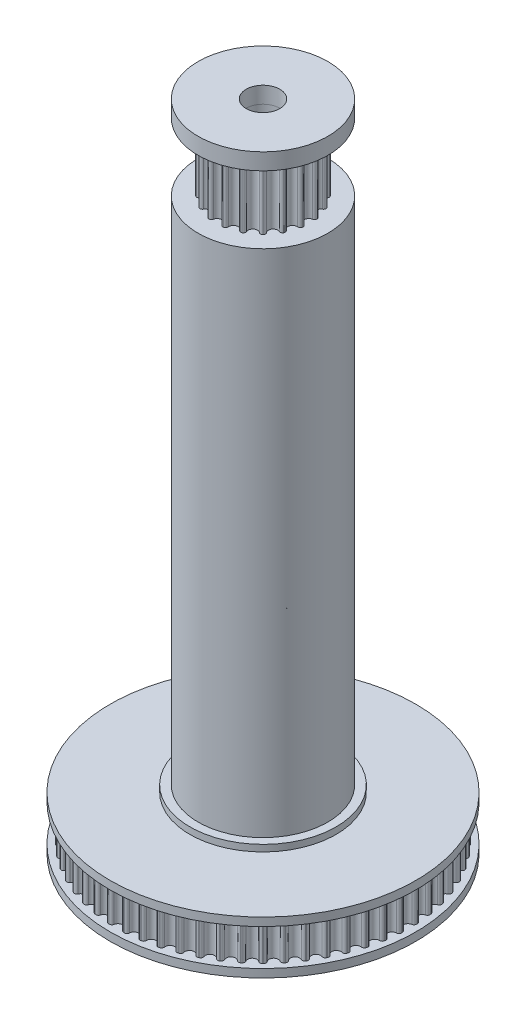
SolidWorks part; units mm, degrees
ref_plane "Front Plane" through (0, 0, 0) normal (0, 0, 1) x (1, 0, 0)
ref_plane "Top Plane" through (0, 0, 0) normal (0, 1, 0) x (1, 0, 0)
ref_plane "Right Plane" through (0, 0, 0) normal (1, 0, 0) x (0, 0, -1)
sketch "PulleyOffsets" plane through (0, 0, 0) normal (1, 0, 0) x (0, 0, -1)
  line L0 (55.5625, 0) -> (-55.5625, 0) construction
  line L1 (55.5625, 111.125) -> (-55.5625, 111.125) construction
  line L2 (0, 0) -> (0, 111.125) construction
  point P7 (0, 0)
  dimension "D1" = 111.125
ref_axis "Axis1" through (0, 34.9332, 0) along (0, -1, 0)
ref_plane "Big Pulley Plane" through (0, 0, 0) normal (0, 1, 0) x (1, 0, 0)
ref_plane "Small Pulley Plane" through (0, 111.125, 0) normal (0, 1, 0) x (1, 0, 0)
sketch "Sketch1" plane through (0, 0, 0) normal (0, 1, 0) x (1, 0, 0)
  line L0 (0, 0) -> (0, 28.2667) construction
  line L1 (0, 0) -> (2.9202, 27.7837) construction
  circle A0 centre (0, 0) radius 28.2667 construction
  circle A1 centre (0, 0) radius 27.0467 construction
  circle A2 centre (0, 27.9367) radius 0.89 construction
  circle A5 centre (2.9202, 27.7837) radius 0.89 construction
  arc A6 (0, 27.0467) -> (0.8804, 27.8061) centre (0, 27.9367) ccw
  arc A7 (0.8804, 27.8061) -> (1.3997, 28.2321) centre (1.3749, 27.7327) cw
  arc A8 (1.559, 28.2237) -> (2.031, 27.7458) centre (1.5314, 27.7245) cw
  arc A9 (2.8272, 26.8986) -> (2.031, 27.7458) centre (2.9202, 27.7837) cw
  arc A10 (1.3997, 28.2321) -> (1.559, 28.2237) centre (0, 0) cw
  arc A11 (0, 27.0467) -> (2.8272, 26.8986) centre (0, 0) ccw
  dimension "D1" = 56.5335
  dimension "D3" = 1.78
  dimension "D4" = 0.5
  dimension "D2" = 1.22
  dimension "D5" = 6
extrude "Boss-Extrude1" add sketch "Sketch1" along normal mid plane 7.112 contours A6 A11 A9 A8 A7 region at (0.001, 0, -0.0192)
pattern_circular "CirPattern1" count 60 over 360 about axis through (0, 34.9332, 0) along (0, -1, 0) of "Boss-Extrude1"
sketch "Sketch2" plane through (0, 0, 0) normal (1, 0, 0) x (0, 0, -1)
  line L10 (0, 3.5) -> (29.4415, 3.5) construction
  line L11 (0, 3.5) -> (0, 5.0875) construction
  line L12 (0, 5.0875) -> (29.4415, 5.0875) construction
  line L15 (29.4415, 3.5) -> (29.4415, 5.0875) construction
  line L20 (0, 34.9332) -> (0, -6.9932) construction
  line L22 (29.4415, 5.0875) -> (0, 5.0875)
  line L23 (29.4415, 5.0875) -> (29.4415, 3.5)
  line L24 (29.4415, 3.5) -> (0, 3.5)
  line L25 (0, 5.0875) -> (0, 3.5)
  dimension "D1" = 1.5875
  dimension "D2" = 29.4415
  dimension "D3" = 3.5
revolve "Revolve3" add sketch "Sketch2" angle 360 about axis through (0, 34.9332, 0) along (0, -1, 0) region at (0, 4.2937, -14.7207)
mirror "Mirror1" about plane through (0, 0, 0) normal (0, 1, 0) of "Revolve3"
sketch "Sketch3" plane through (0, 0, 0) normal (0, 1, 0) x (1, 0, 0)
  circle A0 centre (0, 0) radius 22.225
  dimension "D1" = 44.45
extrude "Cut-Extrude1" [suppressed] cut sketch "Sketch3" against normal through all both and the other way through all
sketch "Sketch6" plane through (0, 0, 0) normal (0, 1, 0) x (1, 0, 0)
  line L0 (0, 0) -> (0, 9.1676) construction
  line L1 (0, 0) -> (2.731, 8.405) construction
  circle A0 centre (0, 0) radius 9.1676 construction
  circle A1 centre (0, 0) radius 7.9476 construction
  circle A2 centre (0, 8.8376) radius 0.89 construction
  circle A5 centre (2.731, 8.405) radius 0.89 construction
  arc A6 (0, 7.9476) -> (0.8721, 8.6598) centre (0, 8.8376) ccw
  arc A7 (0.8721, 8.6598) -> (1.4405, 9.0537) centre (1.362, 8.5599) cw
  arc A8 (1.4277, 9.0557) -> (1.8466, 8.5054) centre (1.3498, 8.5618) cw
  arc A9 (2.4559, 7.5586) -> (1.8466, 8.5054) centre (2.731, 8.405) cw
  arc A10 (1.4405, 9.0537) -> (1.4277, 9.0557) centre (0, 0) cw construction
  arc A11 (0, 7.9476) -> (2.4559, 7.5586) centre (0, 0) ccw
  arc A12 (1.4405, 9.0537) -> (1.4277, 9.0557) centre (0, 0) cw
  dimension "D3" = 1.78
  dimension "D4" = 0.5
  dimension "D2" = 1.22
  dimension "D1" = 18.3352
  dimension "D5" = 18
extrude "Boss-Extrude2" add sketch "Sketch6" along normal mid plane 13 from surface contours A6 A11 A9 A8 A7 region at (0.0089, 0, -0.0564) starting at plane "Small Pulley Plane"
pattern_circular "CirPattern2" count 20 over 360 about axis through (0, 34.9332, 0) along (0, -1, 0) of "Boss-Extrude2"
sketch "Sketch4" plane through (0, 0, 0) normal (0, 0, 1) x (1, 0, 0)
  line L0 (14.0875, 5.0875) -> (-14.0875, 5.0875) construction
  line L1 (29.4415, 5.0875) -> (-29.4415, 5.0875) construction
  line L2 (-14.0875, 5.0875) -> (-14.0875, 6.3575)
  line L3 (-14.0875, 6.3575) -> (-12.5, 6.3575)
  line L4 (-12.5, 6.3575) -> (-12.5, 104.625)
  line L5 (0, 0) -> (0, 120.8) construction
  line L6 (12.5, 6.3575) -> (12.5, 104.625) construction
  line L7 (14.0875, 6.3575) -> (12.5, 6.3575) construction
  line L8 (14.0875, 5.0875) -> (14.0875, 6.3575) construction
  line L9 (-12.5, 104.625) -> (12.5, 104.625) construction
  line L10 (-14.0875, 5.0875) -> (0, 5.0875)
  line L11 (0, 5.0875) -> (0, 104.625)
  line L12 (0, 104.625) -> (-12.5, 104.625)
  line L13 (1.841, 104.625) -> (3.5054, 104.625) construction
  line L14 (0.8721, 117.625) -> (-0.8721, 117.625) construction
  line L15 (-12.5, 120.8) -> (0, 120.8)
  line L16 (-12.5, 120.8) -> (-12.5, 117.625)
  line L17 (-12.5, 117.625) -> (0, 117.625)
  line L18 (0, 120.8) -> (0, 117.625)
  line L19 (-12.5, 104.625) -> (-12.5, 117.625) construction
  point P14 (0, 5.0875)
  dimension "D1" = 1.27
  dimension "D2" = 1.5875
  dimension "D3" = 25
  dimension "D4" = 3.175
revolve "Revolve4" add sketch "Sketch4" angle 360 about L11
sketch "Sketch7" plane through (0, 120.8, 0) normal (0, 1, 0) x (1, 0, 0)
  circle A0 centre (0, 0) radius 3.2385
  dimension "D1" = 6.477
extrude "Cut-Extrude2" cut sketch "Sketch7" against normal through all both and the other way through all
equation "\"TEETH_NUM\"= 60"
equation "\"TOOTH_PITCH\"= 3mm"
equation "\"PITCH_LINE_OFFSET\"= .015in"
equation "\"DIAMETER_PER_GROOVE\"= \"OUTSIDE_DIAMETER\" / \"TEETH_NUM\" * 1in"
equation "\"PITCH_DIAMETER\"= ( ( \"TEETH_NUM\" * 3 - 1.31 ) / 3.1415 + .415 ) * 1mm"
equation "\"OUTSIDE_DIAMETER\"= \"PITCH_DIAMETER\" - \"PITCH_LINE_OFFSET\" * 2"
equation "\"D1@Sketch1\"=\"OUTSIDE_DIAMETER\""
equation "\"TOOTH_HEIGHT\"= 1.22mm"
equation "\"D2@Sketch1\"=\"TOOTH_HEIGHT\""
equation "\"TOOTH_DIAMETER\"= 1.78mm"
equation "\"INTERNAL_RADIUS\"= .5mm"
equation "\"D3@Sketch1\"=\"TOOTH_DIAMETER\""
equation "\"D5@Sketch1\"=360 / \"TEETH_NUM\""
equation "\"D4@Sketch1\"=\"INTERNAL_RADIUS\""
equation "\"D1@CirPattern1\"=\"TEETH_NUM\""
equation "\"BELT_GAP\"= 7mm"
equation "\"D2@Sketch2\"=\"PITCH_DIAMETER\"/2+1/32"
equation "\"D3@Sketch2\"=\"BELT_GAP\"/2"
equation "\"2_TEETH_NUM\"= 20"
equation "\"2_PITCH_DIAMETER\"= ( ( \"2_TEETH_NUM\" * 3 - 1.31 ) / 3.1415 + .415 ) * 1mm"
equation "\"2_OUTSIDE_DIAMETER\"= \"2_PITCH_DIAMETER\" - \"PITCH_LINE_OFFSET\" * 2"
equation "\"2_DIAMETER_PER_GROOVE\"= \"2_OUTSIDE_DIAMETER\" / \"2_TEETH_NUM\" * 1in"
equation "\"D5@Sketch6\"=360/\"2_TEETH_NUM\""
equation "\"D1@Sketch6\"=\"2_OUTSIDE_DIAMETER\""
equation "\"D2@Sketch6\"=\"TOOTH_HEIGHT\""
equation "\"D3@Sketch6\"=\"TOOTH_DIAMETER\""
equation "\"D4@Sketch6\"=\"INTERNAL_RADIUS\""
equation "\"2_BELT_GAP\"= 13mm"
equation "\"D1@CirPattern2\"=\"2_TEETH_NUM\""
equation "\"D1@Boss-Extrude2\"=\"2_BELT_GAP\""
equation "\"Pulley_OffSets\"= 4.375"
equation "\"D1@PulleyOffsets\" = \"Pulley_OffSets\""
